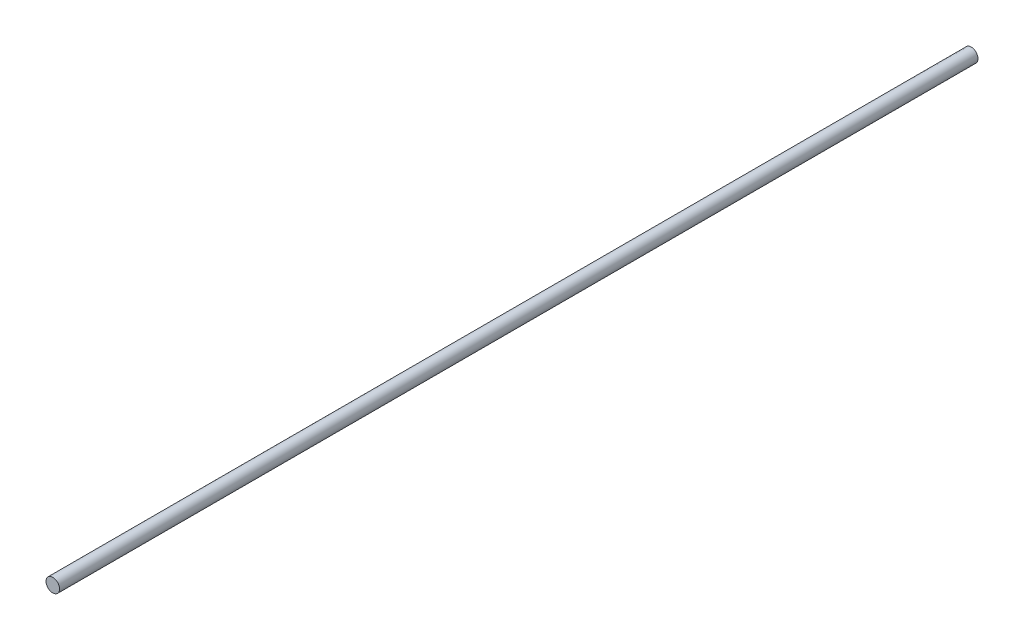
SolidWorks part; units mm, degrees
ref_plane "Front Plane" through (0, 0, 0) normal (0, 0, 1) x (1, 0, 0)
ref_plane "Top Plane" through (0, 0, 0) normal (0, 1, 0) x (1, 0, 0)
ref_plane "Right Plane" through (0, 0, 0) normal (1, 0, 0) x (0, 0, -1)
other "Default"
sketch "Sketch1" plane through (0, 0, 0) normal (0, 0, 1) x (1, 0, 0)
  circle A0 centre (0, 0) radius 4
  dimension "Diameter" = 8
extrude "Boss-Extrude1" add sketch "Sketch1" along normal mid plane 542
